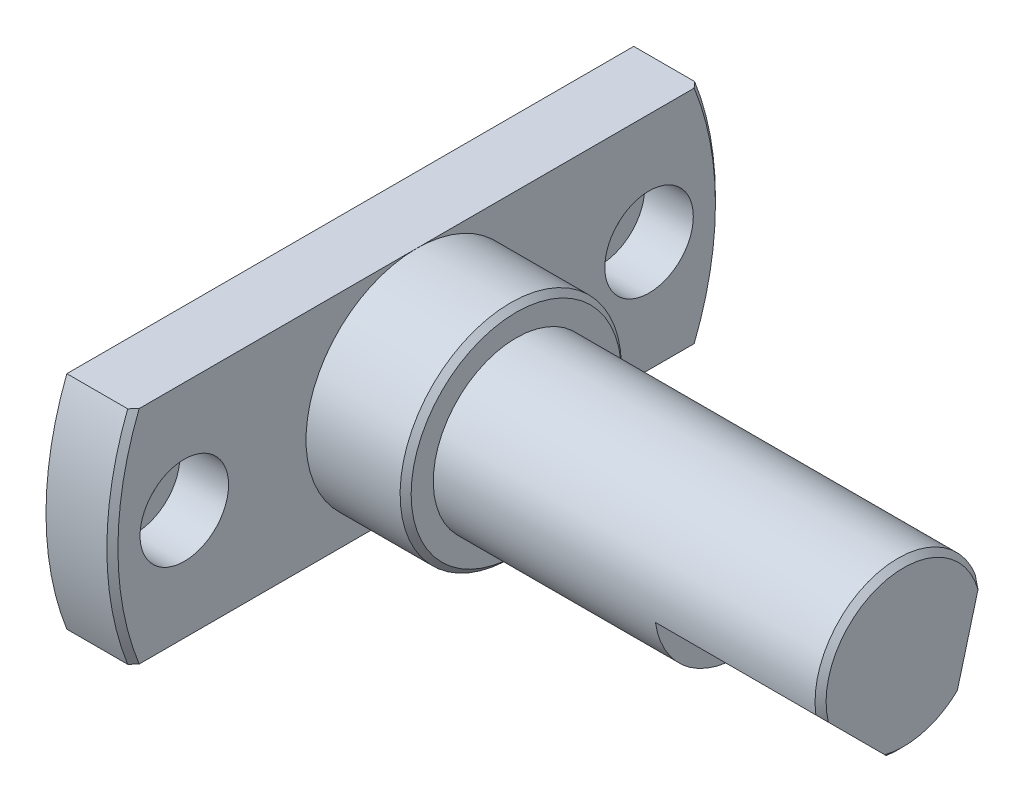
SolidWorks part; units mm, degrees
material "3.1325 (EN-AW 2017A)"
ref_plane "Plan de face" through (0, 0, 0) normal (0, 0, 1) x (1, 0, 0)
ref_plane "Plan de dessus" through (0, 0, 0) normal (0, 1, 0) x (1, 0, 0)
ref_plane "Plan de droite" through (0, 0, 0) normal (1, 0, 0) x (0, 0, -1)
sketch "Esquisse1" plane through (0, 0, 0) normal (0, 0, 1) x (1, 0, 0)
  line L0 (15, 7.5) -> (50, 7.5)
  line L1 (50, 7.5) -> (50, 0)
  line L2 (50, 0) -> (0, 0)
  line L3 (0, 0) -> (0, 27.5)
  line L4 (6, 10) -> (15, 10)
  line L5 (15, 10) -> (15, 7.5)
  line L7 (0, 27.5) -> (6, 27.5)
  line L8 (6, 27.5) -> (6, 10)
  dimension "D1" = 50
  dimension "D3" = 7.5
  dimension "D4" = 15
  dimension "D5" = 6
  dimension "D6" = 10
  dimension "D7" = 20
revolve "Révolution1" add sketch "Esquisse1" angle 360 about L2
chamfer "Chanfrein1" distance 0.5 angle 45 2 edges at (15, 10, 0) (6, 27.5, 0)
hole_wizard "Chambrage pour vis à tête hexagonale M41" positions "Esquisse4" profile "Esquisse2" counterbore size "M4" standard "ISO" end condition through all
sketch "Esquisse4" plane through (6, 0, 0) normal (1, 0, 0) x (0, 0, -1)
  line L0 (21, 0) -> (0, 0) construction
  line L1 (0, 0) -> (-21, 0) construction
  line L2 (0, 5.6863) -> (0, -6.4906) construction
  point P0 (-21, 0)
  point P2 (21, 0)
  dimension "D1" = 42
sketch "Esquisse2" plane through (6, 0, 21) normal (0, 1, 0) x (0, 0, -1)
  line L0 (0, 0) -> (0, 6)
  line L1 (0, 6) -> (2.25, 6)
  line L3 (2.25, 6) -> (2.25, 4.4)
  line L4 (2.25, 4.4) -> (4, 4.4)
  line L5 (4, 4.4) -> (4, 0)
  line L7 (4, 0) -> (0, 0)
  line L11 (0, -6.35) -> (0, 107.95) construction
  dimension "Diamètre du perçage jusqu'au prochain" = 4.5
  dimension "Profondeur du perçage jusqu'au prochain" = 6
  dimension "Diamètre du chambrage" = 8
  dimension "Profondeur du chambrage" = 4.4
sketch "Esquisse8" plane through (50, 0, 0) normal (1, 0, 0) x (0, 0, -1)
  line L0 (-1.0607, -7.4246) -> (-7.4246, -1.0607)
  line L1 (4.6309, -5.8996) -> (6.9602, 2.7938)
  line L2 (0, 14.7202) -> (0, 0) construction
  line L3 (0, 0) -> (10.8159, -2.8981) construction
  arc A0 (-1.0607, -7.4246) -> (-7.4246, -1.0607) centre (0, 0) cw
  circle A1 centre (0, 0) radius 7.5 construction
  arc A3 (4.6309, -5.8996) -> (6.9602, 2.7938) centre (0, 0) ccw
  circle A4 centre (0, 0) radius 7.5 construction
  dimension "D1" = 6
  dimension "D2" = 6
  dimension "D3" = 60
  dimension "D4" = 105
extrude "Enlèv. mat.-Extru.1" cut sketch "Esquisse8" against normal blind 15
sketch "Esquisse9" plane through (6, 0, 0) normal (1, 0, 0) x (0, 0, -1)
  point P0 (-21, 0)
  point P1 (21, 0)
sketch "Esquisse10" plane through (50, 0, 0) normal (1, 0, 0) x (0, 0, -1)
  line L0 (0, 15.042) -> (0, -18.3339) construction
sketch "Esquisse11" plane through (0, 0, 0) normal (-1, 0, 0) x (0, 0, 1)
  line L0 (25.6174, -10) -> (-25.6174, -10)
  line L2 (-33.9621, 0) -> (34.1744, 0) construction
  line L3 (25.6174, 10) -> (-25.6174, 10)
  circle A0 centre (0, 0) radius 27.5 construction
  arc A1 (-25.6174, -10) -> (25.6174, -10) centre (0, 0) ccw
  arc A2 (-25.6174, 10) -> (25.6174, 10) centre (0, 0) cw
  dimension "D1" = 20
extrude "Enlèv. mat.-Extru.2" cut sketch "Esquisse11" against normal through all
chamfer "Chanfrein3" distance 0.5 angle 45 2 edges at (50, -7.2444, -1.9411) (50, 7.2444, 1.9411)
ref_axis "Axe1" through (32, 0, 0) along (1, 0, 0)
